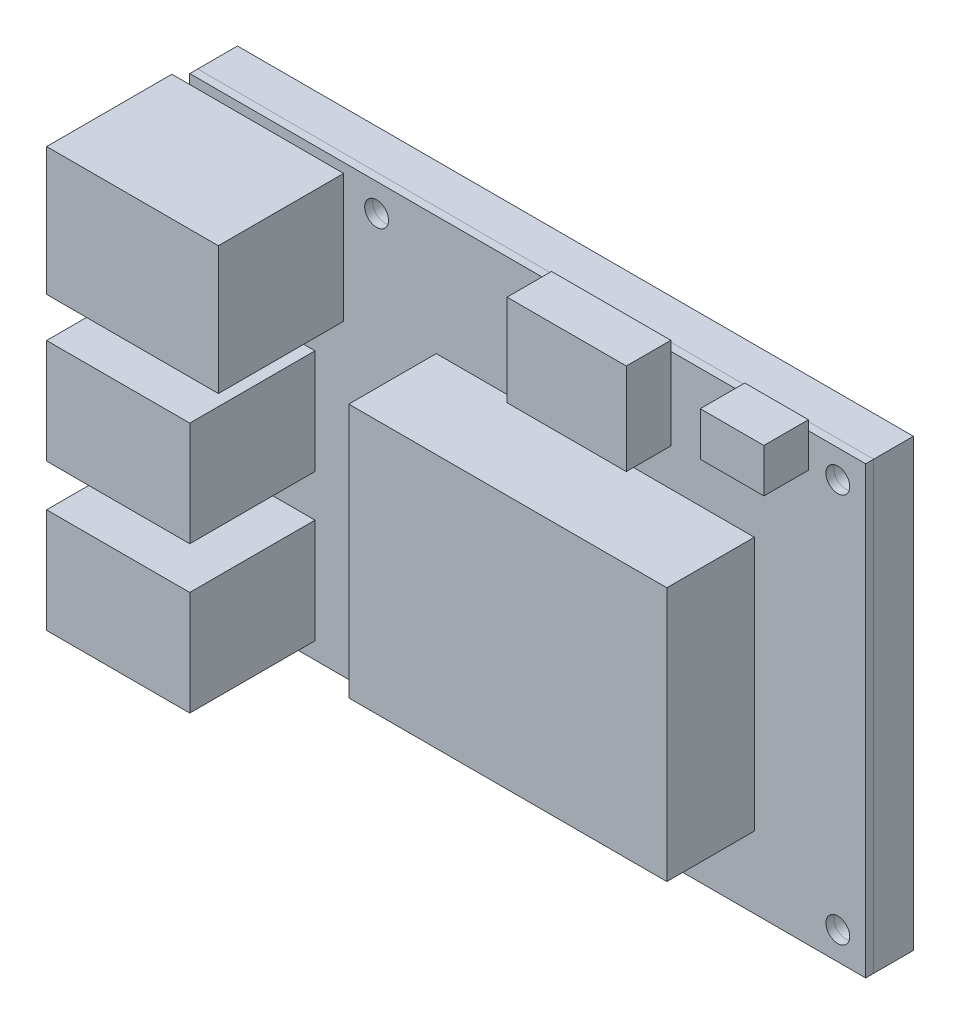
SolidWorks part; units mm, degrees
ref_plane "Front Plane" through (0, 0, 0) normal (0, 0, 1) x (1, 0, 0)
ref_plane "Top Plane" through (0, 0, 0) normal (0, 1, 0) x (1, 0, 0)
ref_plane "Right Plane" through (0, 0, 0) normal (1, 0, 0) x (0, 0, -1)
sketch "Sketch1" plane through (0, 0, 0) normal (0, 0, 1) x (1, 0, 0)
  line L0 (-12.9184, 34.1475) -> (45.0816, 34.1475) construction
  line L1 (-36.4184, 37.6475) -> (48.5816, 37.6475)
  line L2 (-36.4184, 37.6475) -> (-36.4184, -18.3525)
  line L3 (-36.4184, -18.3525) -> (48.5816, -18.3525)
  line L4 (48.5816, 37.6475) -> (48.5816, -18.3525)
  line L5 (45.0816, 34.1475) -> (45.0816, -14.8525) construction
  line L6 (45.0816, -14.8525) -> (-12.9184, -14.8525) construction
  line L7 (-12.9184, -14.8525) -> (-12.9184, 34.1475) construction
  line L8 (45.0816, 9.6475) -> (48.5816, 9.6475) construction
  circle A0 centre (-12.9184, 34.1475) radius 1.5
  circle A1 centre (-12.9184, -14.8525) radius 1.5
  circle A2 centre (45.0816, 34.1475) radius 1.5
  circle A3 centre (45.0816, -14.8525) radius 1.5
  dimension "D1" = 3
  dimension "D2" = 58
  dimension "D3" = 49
  dimension "D4" = 56
  dimension "D5" = 85
  dimension "D6" = 3.5
extrude "Boss-Extrude1" add sketch "Sketch1" along normal blind 1
extrude "Boss-Extrude2" add sketch "Sketch1<2>" against normal blind 5 separate body
sketch "Sketch1<2>" plane through (0, 0, 0) normal (0, 0, 1) x (1, 0, 0) same geometry as "Sketch1"
sketch "Sketch3" plane through (0, 0, 1) normal (0, 0, 1) x (1, 0, 0)
  line L0 (48.5816, 37.6475) -> (48.5816, -18.3525) construction
  line L1 (-5.4184, 22.6475) -> (34.5816, 22.6475)
  line L2 (-5.4184, 22.6475) -> (-5.4184, -9.3525)
  line L3 (-5.4184, -9.3525) -> (34.5816, -9.3525)
  line L4 (34.5816, 22.6475) -> (34.5816, -9.3525)
  line L5 (-36.4184, 37.6475) -> (48.5816, 37.6475) construction
  dimension "D1" = 40
  dimension "D2" = 32
  dimension "D3" = 14
  dimension "D4" = 15
extrude "Boss-Extrude3" add sketch "Sketch3" along normal blind 11
sketch "Sketch4" plane through (0, 0, 1) normal (0, 0, 1) x (1, 0, 0)
  line L0 (-38.6679, 8.7575) -> (-28.6679, 8.7575) construction
  line L1 (-38.6679, 15.3275) -> (-20.6679, 15.3275)
  line L2 (-38.6679, 15.3275) -> (-38.6679, 2.1875)
  line L3 (-38.6679, 2.1875) -> (-20.6679, 2.1875)
  line L4 (-20.6679, 15.3275) -> (-20.6679, 2.1875)
  line L5 (-38.6679, -3.1125) -> (-20.6679, -3.1125)
  line L6 (-38.6679, -3.1125) -> (-38.6679, -16.2525)
  line L7 (-38.6679, -16.2525) -> (-20.6679, -16.2525)
  line L8 (-20.6679, -3.1125) -> (-20.6679, -16.2525)
  line L9 (-38.6679, -9.6825) -> (-28.6679, -9.6825) construction
  line L12 (-38.6679, 36.4475) -> (-17.0679, 36.4475)
  line L13 (-38.6679, 36.4475) -> (-38.6679, 20.3475)
  line L14 (-38.6679, 20.3475) -> (-17.0679, 20.3475)
  line L15 (-17.0679, 36.4475) -> (-17.0679, 20.3475)
  dimension "D1" = 18
  dimension "D2" = 13.14
  dimension "D3" = 10
  dimension "D4" = 5.3
  dimension "D5" = 2.1
  dimension "D6" = 21.6
  dimension "D7" = 1.2
  dimension "D8" = 16.1
extrude "Boss-Extrude4" add sketch "Sketch4" along normal blind 15.75
sketch "Sketch5" plane through (0, 0, 1) normal (0, 0, 1) x (1, 0, 0)
  line L1 (9.0816, 38.8475) -> (24.0816, 38.8475)
  line L2 (9.0816, 38.8475) -> (9.0816, 27.3475)
  line L3 (9.0816, 27.3475) -> (24.0816, 27.3475)
  line L4 (24.0816, 38.8475) -> (24.0816, 27.3475)
  line L5 (33.3816, 38.8475) -> (41.3816, 38.8475)
  line L6 (33.3816, 38.8475) -> (33.3816, 33.3475)
  line L7 (33.3816, 33.3475) -> (41.3816, 33.3475)
  line L8 (41.3816, 38.8475) -> (41.3816, 33.3475)
  dimension "D1" = 15
  dimension "D2" = 8
  dimension "D3" = 11.5
  dimension "D4" = 5.5
  dimension "D5" = 1.2
  dimension "D6" = 24.5
  dimension "D7" = 7.2
extrude "Boss-Extrude5" add sketch "Sketch5" along normal blind 5.6
